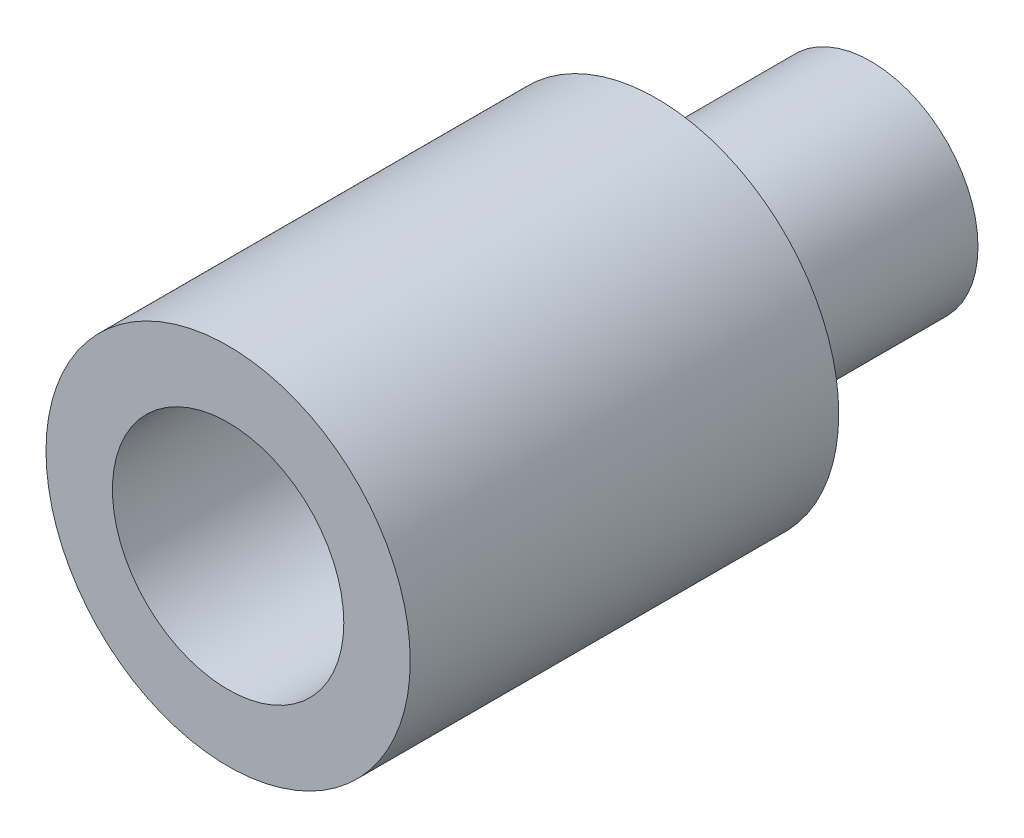
SolidWorks part; units mm, degrees
material "ABS"
ref_plane "X-Y Datum" through (0, 0, 0) normal (0, 0, 1) x (1, 0, 0)
ref_plane "X-Z Datum" through (0, 0, 0) normal (0, 1, 0) x (1, 0, 0)
ref_plane "Y-Z Datum" through (0, 0, 0) normal (1, 0, 0) x (0, 0, -1)
sketch "Sketch1" plane through (0, 0, 0) normal (0, 0, 1) x (1, 0, 0)
  circle A0 centre (0, 0) radius 2.5
  dimension "D1" = 5
extrude "Boss-Extrude1" add sketch "Sketch1" along normal blind 5
sketch "Sketch2" plane through (0, 0, 5) normal (0, 0, 1) x (1, 0, 0)
  circle A0 centre (0, 0) radius 4.25
  circle A1 centre (0, 0) radius 2.7 construction
  dimension "D1" = 5.4
  dimension "D2" = 8.5
extrude "Boss-Extrude2" add sketch "Sketch2" along normal blind 10 contours A0
sketch "Sketch3" plane through (0, 0, 15) normal (0, 0, 1) x (1, 0, 0)
  circle A0 centre (0, 0) radius 2.7
  dimension "D1" = 5.4
extrude "Cut-Extrude1" cut sketch "Sketch3" against normal blind 8
